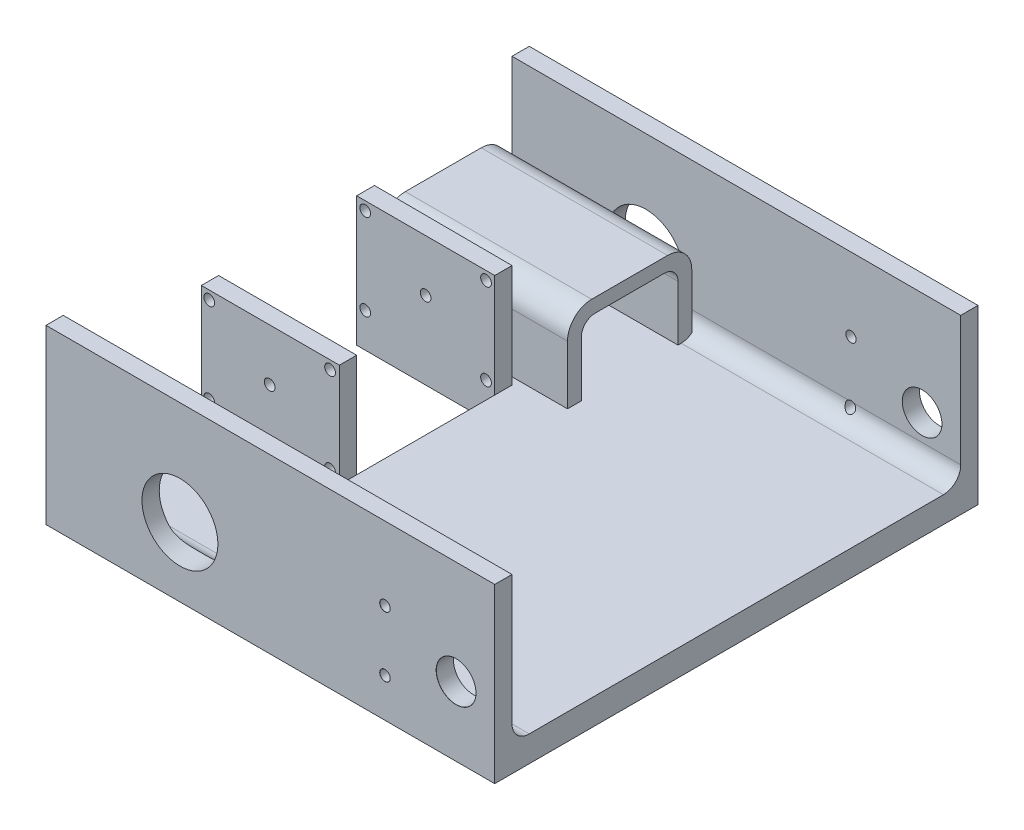
SolidWorks part; units mm, degrees
ref_plane "Front Plane" through (0, 0, 0) normal (0, 0, 1) x (1, 0, 0)
ref_plane "Top Plane" through (0, 0, 0) normal (0, 1, 0) x (1, 0, 0)
ref_plane "Right Plane" through (0, 0, 0) normal (1, 0, 0) x (0, 0, -1)
sketch "Sketch2" plane through (0, 0, 0) normal (0, 1, 0) x (1, 0, 0)
  line L0 (-65, 65) -> (-65, 70)
  line L1 (-65, 65) -> (65, 65)
  line L2 (-65, 65) -> (-65, -65)
  line L3 (-65, -65) -> (65, -65)
  line L4 (65, 65) -> (65, -65)
  line L5 (-65, 65) -> (65, -65) construction
  line L6 (-65, -65) -> (65, 65) construction
  line L7 (65, 70) -> (-65, 70)
  line L8 (65, 70) -> (65, 65)
  line L9 (-71.5, 0) -> (71.5, 0) construction
  line L10 (65, -70) -> (65, -65)
  line L11 (65, -70) -> (-65, -70)
  line L12 (-65, -65) -> (-65, -70)
  line L13 (-65, 20) -> (-65, 25.1643)
  line L14 (-65, -20) -> (-25, -20)
  line L15 (-65, -20) -> (-65, 20)
  line L16 (-65, 20) -> (-25, 20)
  line L17 (-25, -20) -> (-25, 20)
  line L18 (-65, -20) -> (-25, 20) construction
  line L19 (-65, 20) -> (-25, -20) construction
  line L20 (-25, 25) -> (-25.6854, 25.6854)
  line L21 (-65, -20) -> (-65, -25.1343)
  point P0 (0, 0)
  point P12 (-45, 0)
  dimension "D1" = 130
  dimension "D2" = 130
  dimension "D3" = 5
  dimension "D4" = 40
  dimension "D5" = 40
  dimension "D6" = 110
extrude "Boss-Extrude1" add sketch "Sketch2" along normal blind 7.5 contours L4 L1 L2 L3 region at (4.7059, 0, 0)
extrude "Boss-Extrude2" add sketch "Sketch2<4>" along normal blind 50 contours L3 L12 L11 L10 | L8 L7 L0 L1 region at (0, 0, -67.5) region at (0, 0, 67.5)
sketch "Sketch2<4>" plane through (0, 0, 0) normal (0, 1, 0) x (1, 0, 0) same geometry as "Sketch2"
sketch "Sketch5" plane through (0, 0, 70) normal (0, 0, 1) x (1, 0, 0)
  line L0 (-65, 20) -> (65, 20) construction
  line L1 (33.2, 11.25) -> (33.2, 28.75) construction
  line L4 (-65, 50) -> (-65, 0) construction
  line L5 (65, 50) -> (65, 0) construction
  line L6 (65, 0) -> (-65, 0) construction
  point P8 (-26.2, 20)
  point P11 (33.2, 20)
  point P12 (33.2, 28.75)
  point P13 (33.2, 11.25)
  point P14 (53.8, 20)
  dimension "D1" = 20
  dimension "D2" = 17.5
  dimension "D3" = 11.2
  dimension "D4" = 31.8
  dimension "D5" = 80
other "AlignGroup1"
other "AlignGroup2"
sketch "Sketch8" plane through (0, 0, 70) normal (0, 0, 1) x (1, 0, 0)
  point P0 (33.2, 28.75)
  point P3 (33.2, 11.25)
hole_wizard "Ø3.0mm Dowel Hole1" positions "Sketch8" profile "Sketch7" hole size "Ø3.0" standard "DIN" end condition through all
sketch "Sketch7" plane through (33.2, 28.75, 70) normal (1, 0, 0) x (0, -1, 0)
  line L0 (0, 0) -> (0, 140)
  line L1 (0, 140) -> (1.5, 140)
  line L2 (1.5, 140) -> (1.5, 0.025)
  line L3 (1.5, 0.025) -> (1.525, 0)
  line L5 (1.525, 0) -> (0, 0)
  line L6 (-1.5, 0.025) -> (-1.525, 0) construction
  line L11 (0, -6.35) -> (0, 107.95) construction
  dimension "Thru Hole Dia." = 3
  dimension "Thru Hole Depth" = 140
  dimension "Near C'Sink Dia." = 3.05
  dimension "Near C'Sink Angle" = 90
fillet "Fillet1" radius 5 2 edges at (0, 7.5, 65) (0, 7.5, -65)
hole_wizard "Ø11.5 (11.5) Diameter Hole2" positions "3DSketch2" profile "Sketch10" hole size "Ø11.5" standard "ANSI Metric" end condition through all
sketch3d "3DSketch2"
  point P0 (53.8, 20, 70)
sketch "Sketch10" plane through (53.8, 20, 70) normal (1, 0, 0) x (0, -1, 0)
  line L0 (0, 0) -> (0, 140)
  line L1 (0, 140) -> (5.75, 140)
  line L2 (5.75, 140) -> (5.75, 0.025)
  line L3 (5.75, 0.025) -> (5.775, 0)
  line L5 (5.775, 0) -> (0, 0)
  line L6 (-5.75, 0.025) -> (-5.775, 0) construction
  line L11 (0, -6.35) -> (0, 107.95) construction
  dimension "Thru Hole Dia." = 11.5
  dimension "Thru Hole Depth" = 140
  dimension "Near C'Sink Dia." = 11.55
  dimension "Near C'Sink Angle" = 90
hole_wizard "Ø1.0 (22) Diameter Hole1" positions "3DSketch3" profile "Sketch12" hole size "Ø1.0" standard "ANSI Metric"
sketch3d "3DSketch3"
  point P0 (-26.2, 20, 70)
sketch "Sketch12" plane through (-26.2, 20, 70) normal (1, 0, 0) x (0, -1, 0)
  line L0 (0, 0) -> (0, 146.6095)
  line L1 (0, 146.6095) -> (11, 140)
  line L2 (11, 140) -> (11, 0)
  line L5 (11, 0) -> (0, 0)
  line L10 (0, 146.6095) -> (-11, 140) construction
  line L11 (0, -6.35) -> (0, 107.95) construction
  dimension "Hole Dia." = 22
  dimension "Hole Depth" = 140
  dimension "Drill Angle" = 118
sketch "Sketch16" plane through (0, 7.5, 0) normal (0, 1, 0) x (1, 0, 0)
  line L0 (-65, 20) -> (-65, 25.1643)
  line L1 (-25, 25) -> (-65, 25.1643)
  line L2 (-25, 25) -> (-25, 20)
  line L3 (-65, -20) -> (-65, -25)
  line L4 (-65, -20) -> (-65, -60) construction
  line L5 (-65, -25) -> (-25, -25)
  line L6 (-25, -25) -> (-25, -20)
  line L7 (-65, -20) -> (-25, -20) construction
  line L8 (-65, -20) -> (-25, -20) construction
  line L9 (-65, -20) -> (-25, -20)
  line L10 (-65, 20) -> (-25, 20)
  dimension "D1" = 5
  dimension "D2" = 40
  dimension "D3" = 5
extrude "Boss-Extrude3" add sketch "Sketch16" along normal blind 30
sketch "Sketch18" plane through (0.1022, 0, -24.8969) normal (0.0041, 0, -1) x (-1, 0, -0.0041)
  line L0 (25.1025, 22.5) -> (65.1028, 22.5) construction
  line L3 (25.1025, 37.5) -> (25.1025, 7.5) construction
  line L4 (25.1025, 7.5) -> (65.1028, 7.5) construction
  line L5 (45.1026, 7.5) -> (45.1026, 37.5) construction
  line L6 (25.1025, 37.5) -> (65.1028, 37.5) construction
  line L7 (65.1028, 37.5) -> (65.1028, 7.5) construction
  line L9 (27.6026, 35) -> (62.6026, 35) construction
  line L10 (27.6026, 35) -> (27.6026, 10) construction
  line L11 (27.6026, 10) -> (62.6026, 10) construction
  line L12 (62.6026, 35) -> (62.6026, 10) construction
  line L13 (27.6026, 35) -> (62.6026, 10) construction
  line L14 (27.6026, 10) -> (62.6026, 35) construction
  point P6 (45.1026, 22.5)
  point P18 (27.6026, 35)
  point P19 (62.6026, 35)
  point P20 (62.6026, 10)
  point P21 (27.6026, 10)
  point P25 (45.1026, 22.5)
  dimension "D1" = 25
  dimension "D2" = 35
hole_wizard "Ø3.1 (3.1) Diameter Hole1" positions "Sketch18" profile "Sketch20" hole size "Ø3.1" standard "ANSI Metric"
sketch "Sketch20" plane through (-45, 22.5, -25.0821) normal (0, 1, 0) x (-1, 0, -0.0041)
  line L0 (0, 0) -> (0, 51.0962)
  line L1 (0, 51.0962) -> (1.55, 50.1648)
  line L2 (1.55, 50.1648) -> (1.55, 0.025)
  line L3 (1.55, 0.025) -> (1.575, 0)
  line L5 (1.575, 0) -> (0, 0)
  line L6 (-1.55, 0.025) -> (-1.575, 0) construction
  line L10 (0, 51.0962) -> (-1.55, 50.1648) construction
  line L11 (0, -6.35) -> (0, 107.95) construction
  dimension "Hole Dia." = 3.1
  dimension "Hole Depth" = 50.1648
  dimension "Near C'Sink Dia." = 3.15
  dimension "Near C'Sink Angle" = 90
  dimension "Drill Angle" = 118
sketch "Sketch22" plane through (-65, 0, 0) normal (-1, 0, 0) x (0, 0, 1)
  line L0 (-65, 12.5) -> (-25.1643, 12.5) construction
  line L1 (-25.1643, 37.5) -> (-25.1643, 7.5) construction
  line L2 (-45.0821, 17.5) -> (-45.0821, 7.5) construction
  line L3 (-60, 7.5) -> (-25.1643, 7.5) construction
  line L4 (-63.0821, 7.5) -> (-27.0821, 7.5)
  line L5 (-27.0821, 7.5) -> (-27.0821, 31.5)
  line L6 (-63.0821, 7.5) -> (-63.0821, 31.5)
  line L7 (-63.0821, 31.5) -> (-27.0821, 31.5)
  point P10 (-45.0821, 12.5)
  point P13 (-45.0821, 7.5)
  dimension "D1" = 36
  dimension "D2" = 24
extrude "Boss-Extrude4" add sketch "Sketch22" against normal blind 54
sketch "Sketch23" plane through (-11, 0, 0) normal (1, 0, 0) x (0, 0, -1)
  line L0 (63.0821, 8.5629) -> (27.0821, 8.5629) construction
  line L1 (27.0821, 7.5) -> (27.0821, 31.5) construction
  line L2 (45.0821, 8.5629) -> (45.0821, 7.5) construction
  line L3 (60, 7.5) -> (27.0821, 7.5) construction
  line L4 (59.0821, 7.5) -> (31.0821, 7.5)
  line L5 (31.0821, 7.5) -> (31.0821, 27.5)
  line L6 (31.0821, 27.5) -> (59.0821, 27.5)
  line L7 (59.0821, 27.5) -> (59.0821, 7.5)
  point P12 (45.0821, 7.5)
  dimension "D1" = 28
  dimension "D2" = 20
extrude "Cut-Extrude1" cut sketch "Sketch23" against normal blind 50
fillet "Fillet2" radius 4 2 edges at (-36, 27.5, -31.0821) (-36, 27.5, -59.0821)
fillet "Fillet3" radius 7 2 edges at (-38, 31.5, -27.0821) (-38, 31.5, -63.0821)
